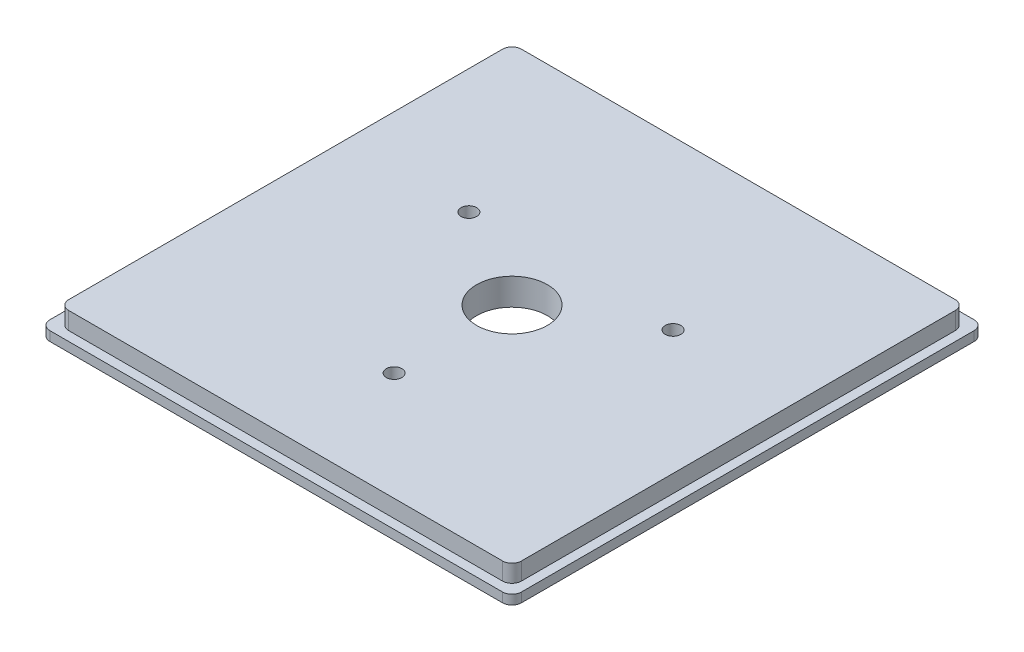
SolidWorks part; units mm, degrees
ref_plane "Plano frontal" through (0, 0, 0) normal (0, 0, 1) x (1, 0, 0)
ref_plane "Plano superior" through (0, 0, 0) normal (0, 1, 0) x (1, 0, 0)
ref_plane "Plano direito" through (0, 0, 0) normal (1, 0, 0) x (0, 0, -1)
sketch "Esboço2" plane through (0, 0, 0) normal (0, 1, 0) x (1, 0, 0)
  line L1 (0, 0) -> (100, 0)
  line L2 (0, 0) -> (0, 100)
  line L3 (0, 100) -> (100, 100)
  line L4 (100, 0) -> (100, 100)
  line L5 (2, 2) -> (98, 2)
  line L6 (2, 2) -> (2, 98)
  line L7 (2, 98) -> (98, 98)
  line L8 (98, 2) -> (98, 98)
sketch "Esboço4" plane through (0, 0, 0) normal (0, 1, 0) x (1, 0, 0)
  circle A0 centre (50, 50) radius 7.5
  circle A1 centre (50, 25) radius 1.65
  circle A2 centre (28.3494, 62.5) radius 1.65
  circle A3 centre (71.6506, 62.5) radius 1.65
  point P10 (50, 50)
  dimension "D1" = 3
extrude "Ressalto-extrusão1" add sketch "Esboço2" along normal blind 2 contours L1 L4 L3 L2 L8 L5 L6 L7 | L5 L8 L7 L6 region at (1.4142, 0, -50) region at (50, 0, -50)
extrude "Ressalto-extrusão2" add sketch "Esboço2<3>" along normal blind 5.7 contours L6 L7 L8 L5
sketch "Esboço2<3>" plane through (0, 0, 0) normal (0, 1, 0) x (1, 0, 0) same geometry as "Esboço2"
fillet "Filete2" radius 2 8 edges at (0, 1, 0) (2, 3.85, -2) (100, 1, 0) (98, 3.85, -2) (100, 1, -100) (98, 3.85, -98) (0, 1, -100) (2, 3.85, -98)
extrude "Corte-extrusão1" cut sketch "Esboço4" along normal through all
